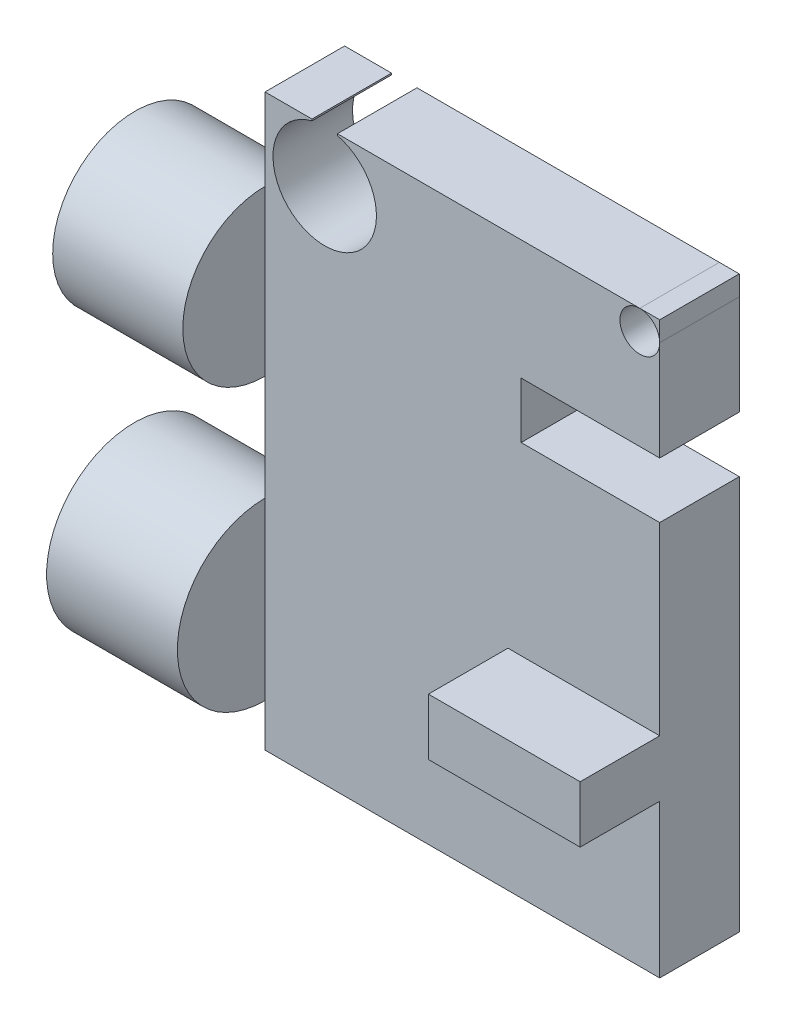
SolidWorks part; units mm, degrees
ref_plane "前视基准面" through (0, 0, 0) normal (0, 0, 1) x (1, 0, 0)
ref_plane "上视基准面" through (0, 0, 0) normal (0, 1, 0) x (1, 0, 0)
ref_plane "右视基准面" through (0, 0, 0) normal (1, 0, 0) x (0, 0, -1)
sketch "草图1" plane through (0, 0, 0) normal (0, 0, 1) x (1, 0, 0)
  line L0 (0, 0) -> (-49.6103, 0)
  line L1 (-49.6103, 0) -> (-49.6103, 71.6556)
  line L6 (-49.6103, 71.6556) -> (0, 71.6556)
  line L7 (0, 71.6556) -> (0, 0)
extrude "凸台-拉伸1" add sketch "草图1" along normal blind 10
sketch "草图2" plane through (0, 0, 10) normal (0, 0, 1) x (1, 0, 0)
  line L0 (-49.6103, 61.383) -> (-65.9666, 61.383)
  line L1 (-49.6103, 71.6556) -> (-49.6103, 0) construction
  line L2 (-65.9666, 61.383) -> (-65.9666, 51.0439)
  line L3 (-65.9666, 51.0439) -> (-49.6103, 51.0439)
  line L4 (-49.6103, 61.383) -> (-49.6103, 51.0439)
  line L8 (0, 0) -> (0, 71.6556)
  line L9 (0, 71.6556) -> (-49.6103, 71.6556)
  line L10 (-49.6103, 71.6556) -> (-49.6103, 0)
  line L11 (-49.6103, 0) -> (0, 0)
  line L14 (-49.6103, 61.383) -> (-49.6103, 51.0439)
  dimension "D1" = 0
revolve "旋转1" add sketch "草图2" angle 360 about L3
sketch "草图3" plane through (0, 0, 10) normal (0, 0, 1) x (1, 0, 0)
  line L0 (-49.6103, 40.7048) -> (-49.6103, 0) construction
  line L1 (-49.6103, 27.4394) -> (-66.0491, 27.4394)
  line L2 (-49.6103, 27.4394) -> (-49.6103, 16.4175)
  line L3 (-49.6103, 16.4175) -> (-66.0491, 16.4175) construction
  line L4 (-66.0491, 27.4394) -> (-66.0491, 16.4175)
  line L5 (-66.0491, 16.4175) -> (-49.6103, 16.4175)
revolve "旋转2" add sketch "草图3" angle 360 about L3
sketch "草图4" plane through (0, 0, 10) normal (0, 0, 1) x (1, 0, 0)
  line L0 (0, 0) -> (0, 71.6556) construction
  line L1 (0, 56.6036) -> (-17.4183, 56.6036)
  line L2 (0, 56.6036) -> (0, 49.5808)
  line L3 (0, 49.5808) -> (-17.4183, 49.5808)
  line L4 (-17.4183, 56.6036) -> (-17.4183, 49.5808)
  line L6 (0, 26.3665) -> (-19.0764, 26.3665)
  line L7 (0, 26.3665) -> (0, 19.2462)
  line L8 (0, 19.2462) -> (-19.0764, 19.2462)
  line L9 (-19.0764, 26.3665) -> (-19.0764, 19.2462)
  line M1 (0, 0) -> (0, 71.6556)
extrude "切除-拉伸1" cut sketch "草图4" against normal blind 10 contours L1 L4 L3 M1 region at (-8.7091, 53.0922, 10)
extrude "凸台-拉伸2" add sketch "草图4<3>" along normal blind 10 contours L6 L9 L8 M1 region at (-9.5382, 22.8063, 10)
sketch "草图4<3>" plane through (0, 0, 10) normal (0, 0, 1) x (1, 0, 0) same geometry as "草图4"
sketch "草图5" plane through (0, 0, 10) normal (0, 0, 1) x (1, 0, 0)
  line L0 (-42.1103, 65.1556) -> (-42.1103, 71.6556) construction
  line L5 (0, 71.6556) -> (-49.6103, 71.6556) construction
  line L10 (-43.7103, 71.6556) -> (-43.7103, 71.4556)
  line L11 (-40.5103, 71.6556) -> (-40.5103, 71.4556)
  line L12 (-49.6103, 71.6556) -> (-49.6103, 61.383) construction
  line L13 (-43.7103, 71.6556) -> (-40.5103, 71.6556)
  arc A0 (-43.7103, 71.4556) -> (-40.5103, 71.4556) centre (-42.1103, 65.1556) ccw
  dimension "D4" = 7.5
  dimension "D1" = 0.2
  dimension "D3" = 6.5
extrude "切除-拉伸3" cut sketch "草图5" against normal through all
sketch "草图6" plane through (0, 0, 10) normal (0, 0, 1) x (1, 0, 0)
  line L2 (0, 71.6556) -> (-40.5103, 71.6556) construction
  line L3 (0, 56.6036) -> (0, 71.6556) construction
  circle A0 centre (-2.5, 69.1556) radius 2.5
  dimension "D1" = 5
extrude "切除-拉伸4" cut sketch "草图6" against normal through all
